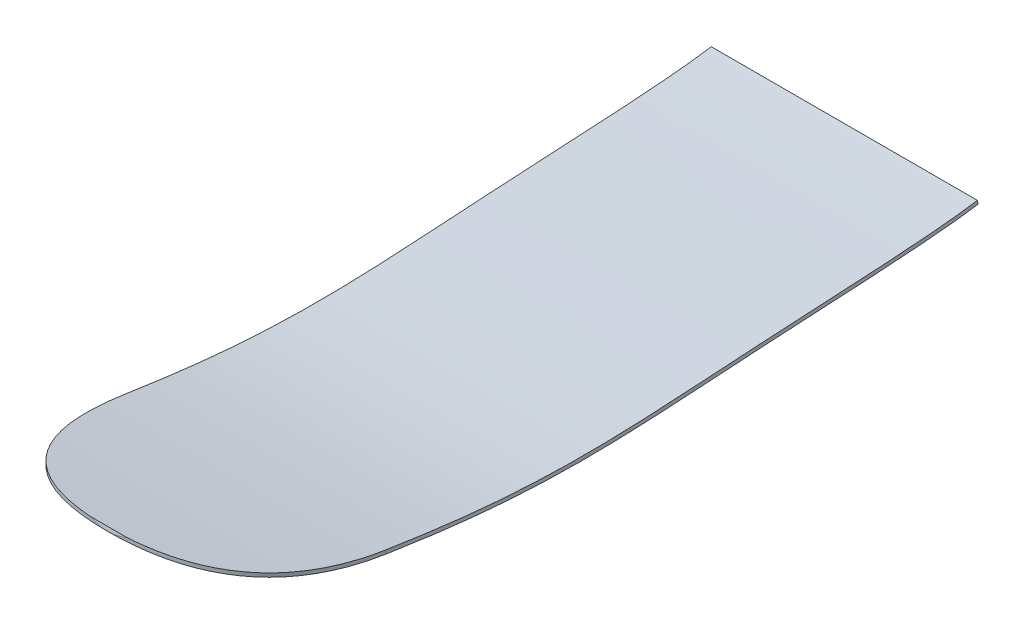
SolidWorks part; units mm, degrees
ref_plane "Front Plane" through (0, 0, 0) normal (0, 0, 1) x (1, 0, 0)
ref_plane "Top Plane" through (0, 0, 0) normal (0, 1, 0) x (1, 0, 0)
ref_plane "Right Plane" through (0, 0, 0) normal (1, 0, 0) x (0, 0, -1)
sketch "Sketch1" plane through (0, 0, 0) normal (1, 0, 0) x (0, 0, -1)
  line L22 (-2674.5928, 189.4475) -> (-2679.5418, 164.9422)
  line L23 (2303.6193, 62.5026) -> (2307.638, 37.8277)
  spline S0 degree 3 poles (-2674.5928, 189.4475) (-2673.7217, 189.2715) (-2665.3829, 187.5894) (-2632.6773, 181.0824) (-2560.4618, 166.9277) (-2453.159, 146.3496) (-2321.8687, 121.9663) (-2214.229, 102.4167) (-2100.0973, 82.2024) (-1981.9486, 61.8633) (-1862.0005, 41.8724) (-1742.1876, 22.6321) (-1604.4823, 1.449) (-1471.3911, -17.7584) (-1372.2601, -30.9609) (-1319.8977, -37.6077) (-1289.7692, -41.3529) (-1266.5258, -44.163) (-1241.4742, -47.1298) (-1222.8796, -49.2917) (-1204.5239, -51.3731) (-1163.9854, -55.912) (-1098.8577, -62.7984) (-970.7023, -74.884) (-830.1088, -85.4815) (-672.7373, -93.8975) (-530.0903, -98.6626) (-388.1599, -100.5517) (-251.2893, -99.8455) (-73.3434, -95.997) (100.8188, -88.5226) (276.9165, -78.6787) (411.4027, -70.3953) (549.8328, -61.4964) (669.8766, -53.8108) (757.1626, -48.4231) (808.1575, -45.3657) (937.1963, -37.7789) (1112.3001, -28.3403) (1330.6018, -16.644) (1547.4995, -4.6424) (1757.3476, 8.2073) (2046.4063, 29.9454) (2209.436, 47.1632) (2303.6193, 62.5026) knots 0.001962 0.001962 0.001962 0.001962 0.015625 0.03125 0.046875 0.078125 0.09375 0.109375 0.125 0.140625 0.15625 0.171875 0.1875 0.210938 0.226562 0.230469 0.234375 0.240234 0.241211 0.246094 0.249023 0.25 0.265625 0.28125 0.316406 0.34375 0.375 0.40625 0.4375 0.46875 0.53125 0.5625 0.59375 0.625 0.65625 0.671875 0.679688 0.6875 0.75 0.78125 0.8125 0.875 0.90625 1 1 1 1
  spline S1 degree 1 poles (-2679.5418, 164.9422) (2307.638, 37.8277) knots 0 0 1 1 construction
  spline S2 degree 3 poles (-2679.5418, 164.9422) (-2679.4632, 164.9263) (-2679.3281, 164.8991) (-2678.8801, 164.8087) (-2678.1108, 164.6536) (-2676.8173, 164.3934) (-2674.6173, 163.9513) (-2670.978, 163.2217) (-2665.216, 162.0701) (-2658.0886, 160.6503) (-2646.8109, 158.4112) (-2629.4678, 154.9843) (-2603.74, 149.9373) (-2573.4061, 144.0323) (-2538.7822, 137.3464) (-2500.2163, 129.9614) (-2458.0519, 121.9586) (-2397.4932, 110.5725) (-2314.5275, 95.2017) (-2206.1364, 75.5684) (-2091.5546, 55.3348) (-1973.2153, 35.0305) (-1853.2919, 15.1181) (-1733.6734, -4.0102) (-1615.9678, -22.0295) (-1501.5051, -38.6801) (-1391.3495, -53.7631) (-1286.3485, -67.1269) (-1187.2262, -78.6416) (-1092.8102, -88.5226) (-1002.6091, -96.9357) (-916.1072, -104.0256) (-805.1779, -111.8656) (-673.7323, -118.939) (-524.971, -123.7848) (-383.0616, -125.5688) (-246.1726, -124.7756) (-112.6826, -121.8185) (18.9101, -117.0636) (150.0175, -110.8251) (282.0566, -103.4174) (416.4658, -95.1241) (531.7185, -87.7119) (626.7063, -81.6268) (699.5653, -77.0232) (774.2767, -72.4178) (851.1896, -67.8589) (929.5902, -63.3869) (1035.7532, -57.5045) (1170.7741, -50.2438) (1334.2001, -41.4857) (1496.5928, -32.494) (1655.5016, -23.0742) (1782.9413, -14.7016) (1880.6588, -7.5895) (1951.5163, -2.0228) (2019.6302, 3.8025) (2084.6927, 9.9124) (2136.1143, 15.2635) (2175.4224, 19.7139) (2203.9518, 23.1401) (2231.4927, 26.6587) (2253.5898, 29.671) (2270.7368, 32.1311) (2283.3291, 34.0021) (2293.5897, 35.5824) (2301.6703, 36.8619) (2305.6437, 37.5029) (2307.638, 37.8277) knots 0.001962 0.001962 0.001962 0.001962 0.002937 0.003912 0.005861 0.00781 0.009759 0.013658 0.017557 0.021455 0.025354 0.033151 0.040948 0.048745 0.056542 0.06434 0.072137 0.079934 0.095528 0.111123 0.126717 0.142311 0.157906 0.1735 0.189094 0.204689 0.220283 0.235877 0.251472 0.267066 0.28266 0.298255 0.313849 0.345038 0.376226 0.407415 0.438604 0.469792 0.500981 0.53217 0.563358 0.594547 0.625736 0.64133 0.656925 0.672519 0.688113 0.703708 0.719302 0.750491 0.781679 0.812868 0.844057 0.875245 0.89084 0.906434 0.922028 0.937623 0.953217 0.961014 0.968811 0.976608 0.984406 0.988304 0.992203 0.996101 0.998051 1 1 1 1
  dimension "D1" = 25
extrude "Boss-Extrude1" add sketch "Sketch1" along normal blind 1524 and the other way blind 1524
sketch "Sketch3" plane through (0, 0, 0) normal (0, 1, 0) x (1, 0, 0)
  line L0 (-900, 2541.7662) -> (900, 2541.7662)
  line L1 (-900, 2541.7662) -> (-900, -1639.0762)
  line L2 (900, 2541.7662) -> (900, -1696.7912)
  line L3 (0, 2955.5244) -> (0, -2061.9995) construction
  line L4 (-2830.2932, 3840.744) -> (2901.1641, 3840.744)
  line L5 (-2830.2932, 3840.744) -> (-2830.2932, -4162.5619)
  line L6 (-2830.2932, -4162.5619) -> (2901.1641, -4162.5619)
  line L7 (2901.1641, 3840.744) -> (2901.1641, -4162.5619)
  line L8 (-94.9374, 0) -> (0, 0) construction
  line L10 (-694.5465, -2679.5418) -> (351.3763, -2679.5418) construction
  line L11 (-1524, 1954.9582) -> (1524, 1954.9582) construction
  line L12 (-1524, -2679.5418) -> (1524, -2679.5418) construction
  spline S0 degree 2 poles (-900, -1639.0762) (-900, -2679.5418) (0, -2679.5418) knots 0 0 0 1 1 1
  spline S1 degree 2 poles (900, -1696.7912) (900, -2679.5418) (0, -2679.5418) knots 0 0 0 1 1 1
  point P15 (0, -2679.5418)
  point P19 (351.3763, -2679.5418)
  point P21 (0, 0)
  dimension "D1" = 1800
extrude "Cut-Extrude1" cut sketch "Sketch3" against normal through all both and the other way through all
